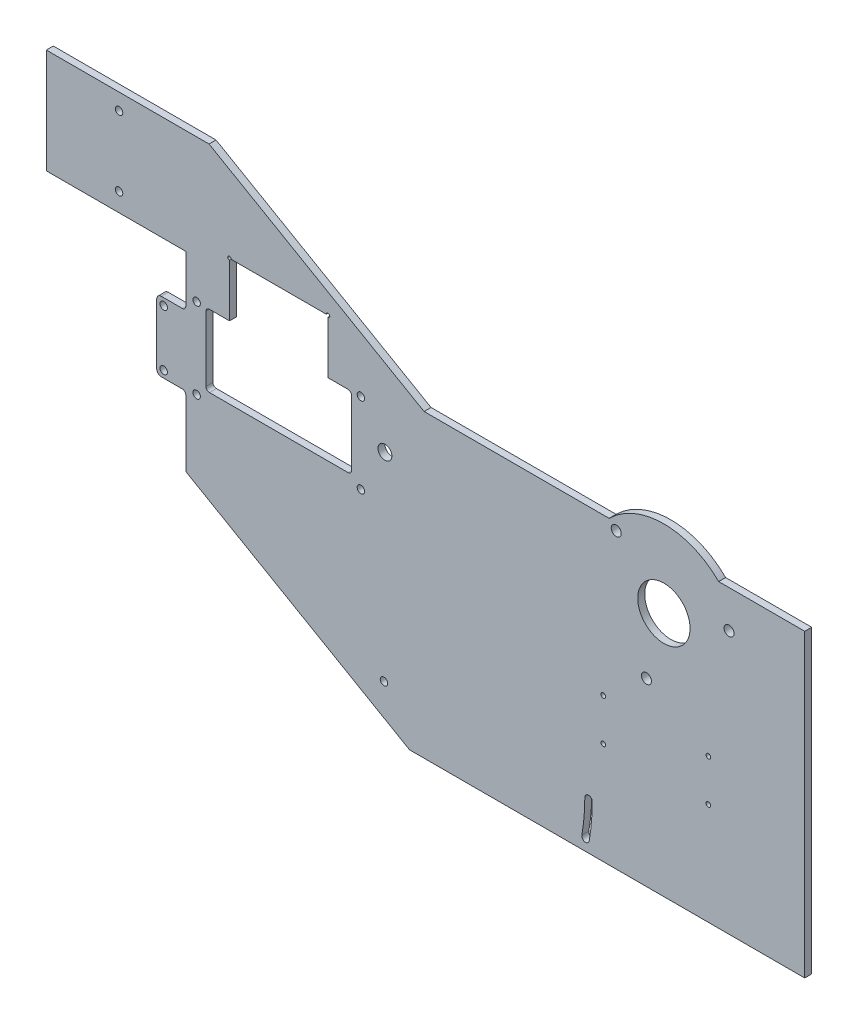
SolidWorks part; units mm, degrees
material "Thornel Mat VMA"
ref_plane "Front Plane" through (0, 0, 0) normal (0, 0, 1) x (1, 0, 0)
ref_plane "Top Plane" through (0, 0, 0) normal (0, 1, 0) x (1, 0, 0)
ref_plane "Right Plane" through (0, 0, 0) normal (1, 0, 0) x (0, 0, -1)
sketch "Sketch1" plane through (0, 0, 0) normal (0, 0, 1) x (1, 0, 0)
  line L1 (20.2869, 47.6) -> (204.7012, 47.6)
  line L2 (20.2869, 47.6) -> (20.2869, -36.0143)
  line L3 (20.2869, -36.0143) -> (204.7012, -36.0143)
  line L4 (204.7012, 47.6) -> (204.7012, -36.0143)
extrude "Boss-Extrude1" add sketch "Sketch1" along normal blind 3
sketch "Sketch2" plane through (0, 0, 0) normal (0, 0, -1) x (-1, 0, 0)
  circle A0 centre (-24.1169, 24) radius 3
  dimension "D1" = 6
extrude "Cut-Extrude1" cut sketch "Sketch2" against normal blind 70
sketch "Sketch3" plane through (0, 0, 3) normal (0, 0, 1) x (1, 0, 0)
  line L0 (24.1169, 24) -> (144.1169, 24) construction
  circle A0 centre (144.1169, 24) radius 11.25
  dimension "D2" = 22.5
  dimension "D1" = 120
extrude "Cut-Extrude2" cut sketch "Sketch3" against normal blind 3
sketch "Sketch4" plane through (0, 0, 3) normal (0, 0, 1) x (1, 0, 0)
  line L0 (-61.5431, 47.6) -> (-61.5431, -3) construction
  line L1 (-61.5431, 56) -> (-61.5431, 34)
  line L2 (-61.5431, 4) -> (-61.5431, -26)
  line L3 (-61.5431, 34) -> (-72.0431, 34)
  line L5 (-61.5431, 4) -> (-72.0431, 4)
  line L6 (-74.0431, 32) -> (-74.0431, 6)
  line L7 (-51.5431, 101) -> (-121.5431, 101)
  line L8 (-121.5431, 101) -> (-121.5431, 56)
  line L9 (-121.5431, 56) -> (-61.5431, 56)
  line L10 (-51.5431, 101) -> (40.9484, 47.6)
  line L11 (20.2869, 47.6) -> (20.2869, -36.0143)
  line L12 (20.2869, -36.0143) -> (204.7012, -36.0143)
  line L13 (204.7012, -36.0143) -> (204.7012, 47.6)
  line L14 (204.7012, 47.6) -> (20.2869, 47.6)
  line L15 (20.2869, 47.6) -> (20.2869, -36.0143)
  line L16 (20.2869, -36.0143) -> (204.7012, -36.0143)
  line L18 (40.9484, 47.6) -> (20.2869, 47.6)
  line L19 (-61.5431, -26) -> (34.7012, -81.5667)
  line L20 (34.7012, -81.5667) -> (204.7012, -81.5667)
  line L21 (204.7012, -81.5667) -> (204.7012, -36.0143)
  line L22 (-85.0431, 56) -> (-64.7431, 56) construction
  circle A0 centre (-71.0431, 31) radius 1.6
  circle A1 centre (-71.0431, 7) radius 1.6
  arc A2 (-72.0431, 4) -> (-74.0431, 6) centre (-72.0431, 6) cw
  arc A3 (-72.0431, 34) -> (-74.0431, 32) centre (-72.0431, 32) ccw
  dimension "D1" = 3.2
  dimension "D2" = 3
  dimension "D5" = 2
  dimension "D3" = 3
  dimension "D4" = 3
  dimension "D7" = 60
  dimension "D8" = 45
  dimension "D9" = 30
  dimension "D10" = 30
  dimension "D11" = 70
  dimension "D12" = 170
  dimension "D6" = 0
extrude "Boss-Extrude2" add sketch "Sketch4" against normal blind 3
sketch "Sketch5" plane through (0, 0, 3) normal (0, 0, 1) x (1, 0, 0)
  line L0 (-0.5431, 62.6) -> (-42.5431, 62.6) construction
  line L1 (8.2869, 8.5) -> (-51.3731, 8.5)
  line L2 (9.7869, 10) -> (9.7869, 38)
  line L3 (8.2869, 39.5) -> (-0.3431, 39.5)
  line L4 (-52.8731, 10) -> (-52.8731, 38)
  line L5 (-41.9931, 62.8) -> (-1.0931, 62.8)
  line L6 (-42.7431, 62.05) -> (-42.7431, 39.5)
  line L8 (-0.3431, 62.05) -> (-0.3431, 39.5)
  line L9 (-42.5431, 57.6) -> (-42.5431, 52.6) construction
  line L10 (-0.5431, 62.6) -> (-0.5431, 57.6) construction
  line L11 (-42.7431, 39.5) -> (-51.3731, 39.5)
  line L13 (7.7869, 47.6) -> (7.7869, -3) construction
  line L14 (-50.8731, -3) -> (-50.8731, 47.6) construction
  line L15 (8.4569, 34.5) -> (-51.5431, 34.5) construction
  line L16 (-51.5431, 13.5) -> (8.4569, 13.5) construction
  arc A0 (9.7869, 38) -> (8.2869, 39.5) centre (8.2869, 38) ccw
  arc A1 (8.2869, 8.5) -> (9.7869, 10) centre (8.2869, 10) ccw
  arc A2 (-51.3731, 8.5) -> (-52.8731, 10) centre (-51.3731, 10) cw
  arc A3 (-51.3731, 39.5) -> (-52.8731, 38) centre (-51.3731, 38) ccw
  arc A4 (-41.9931, 62.8) -> (-42.7431, 62.05) centre (-42.7431, 62.8) ccw
  arc A6 (-1.0931, 62.8) -> (-0.3431, 62.05) centre (-0.3431, 62.8) cw
  dimension "D8" = 1.5
  dimension "D9" = 1.5
  dimension "D10" = 0.75
  dimension "D1" = 0.2
  dimension "D2" = 0.2
  dimension "D3" = 0.2
  dimension "D4" = 2
  dimension "D5" = 2
  dimension "D6" = 5
  dimension "D7" = 5
extrude "Cut-Extrude3" cut sketch "Sketch5" against normal blind 10 contours L8 L5 L6 L3 | L4 L1 L2 L3 region at (-21.5431, 33.186, 3)
sketch "Sketch6" plane through (0, 0, 3) normal (0, 0, 1) x (1, 0, 0)
  line L0 (-61.5431, -3) -> (-50.8731, -3) construction
  line L1 (13.7869, 5) -> (-56.8731, 5) construction
  line L2 (13.7869, 5) -> (13.7869, 39.6) construction
  line L3 (13.7869, 39.6) -> (-56.8731, 39.6) construction
  line L4 (-56.8731, 5) -> (-56.8731, 39.6) construction
  line L5 (-61.5431, 47.6) -> (-50.8731, 47.6) construction
  line L6 (-52.8731, 10) -> (-52.8731, 38) construction
  line L7 (9.7869, 10) -> (9.7869, 38) construction
  circle A0 centre (13.7869, 5) radius 1.6
  circle A1 centre (13.7869, 39.6) radius 1.6
  circle A2 centre (-56.8731, 5) radius 1.6
  circle A3 centre (-56.8731, 39.6) radius 1.6
  dimension "D5" = 3.2
  dimension "D1" = 8
  dimension "D2" = 8
  dimension "D3" = 4
  dimension "D4" = 4
extrude "Cut-Extrude4" cut sketch "Sketch6" against normal blind 3
fillet "Fillet1" radius 1.5 2 edges at (-61.5431, 4, 1.5) (-61.5431, 34, 1.5)
sketch "Sketch8" plane through (0, 0, 3) normal (0, 0, 1) x (1, 0, 0)
  circle A0 centre (-90.2431, 94) radius 1.6
  circle A1 centre (-90.2431, 64) radius 1.6
  dimension "D1" = 3.2
extrude "Cut-Extrude6" cut sketch "Sketch8" against normal blind 12
sketch "Sketch9" plane through (0, 0, 0) normal (0, 0, -1) x (-1, 0, 0)
  circle A0 centre (-172.1287, 31.5058) radius 2.15
  circle A1 centre (-123.6108, 44.5061) radius 2.15
  circle A2 centre (-136.6111, -4.0118) radius 2.15
  dimension "D1" = 4.3
extrude "Cut-Extrude7" cut sketch "Sketch9" against normal blind 12
sketch "Sketch10" plane through (0, 0, 0) normal (0, 0, -1) x (-1, 0, 0)
  line L0 (-204.7012, 47.6) -> (-40.9484, 47.6) construction
  line L1 (-167.6809, 47.6) -> (-120.5529, 47.6)
  arc A0 (-120.5529, 47.6) -> (-167.6809, 47.6) centre (-144.1169, 24) ccw
  dimension "D1" = 66.7
extrude "Boss-Extrude3" add sketch "Sketch10" against normal blind 3
sketch "Sketch12" plane through (0, 0, 3) normal (0, 0, 1) x (1, 0, 0)
  line L0 (34.7012, -81.5667) -> (204.7012, -81.5667) construction
  circle A0 centre (23.7012, -61.5667) radius 1.6
  arc A1 (111.7012, -61.5667) -> (110.4134, -76.5667) centre (23.7012, -61.5667) cw construction
  arc A2 (110.1012, -61.5667) -> (108.8368, -76.294) centre (23.7012, -61.5667) cw
  arc A3 (113.3012, -61.5667) -> (111.99, -76.8394) centre (23.7012, -61.5667) cw
  arc A4 (113.3012, -61.5667) -> (110.1012, -61.5667) centre (111.7012, -61.5667) ccw
  arc A5 (111.99, -76.8394) -> (108.8368, -76.294) centre (110.4134, -76.5667) cw
  dimension "D1" = 3.2
  dimension "D2" = 1.6
  dimension "D3" = 5
extrude "Cut-Extrude8" cut sketch "Sketch12" against normal blind 10
sketch "Sketch13" plane through (0, 0, 0) normal (0, 0, -1) x (-1, 0, 0)
  circle A0 centre (-163.2569, -19.6667) radius 1
  circle A1 centre (-163.2569, -37.6667) radius 1
  circle A2 centre (-118.0569, -19.6667) radius 1
  circle A3 centre (-118.0569, -37.6667) radius 1
  dimension "D1" = 2
extrude "Cut-Extrude9" cut sketch "Sketch13" against normal blind 10
